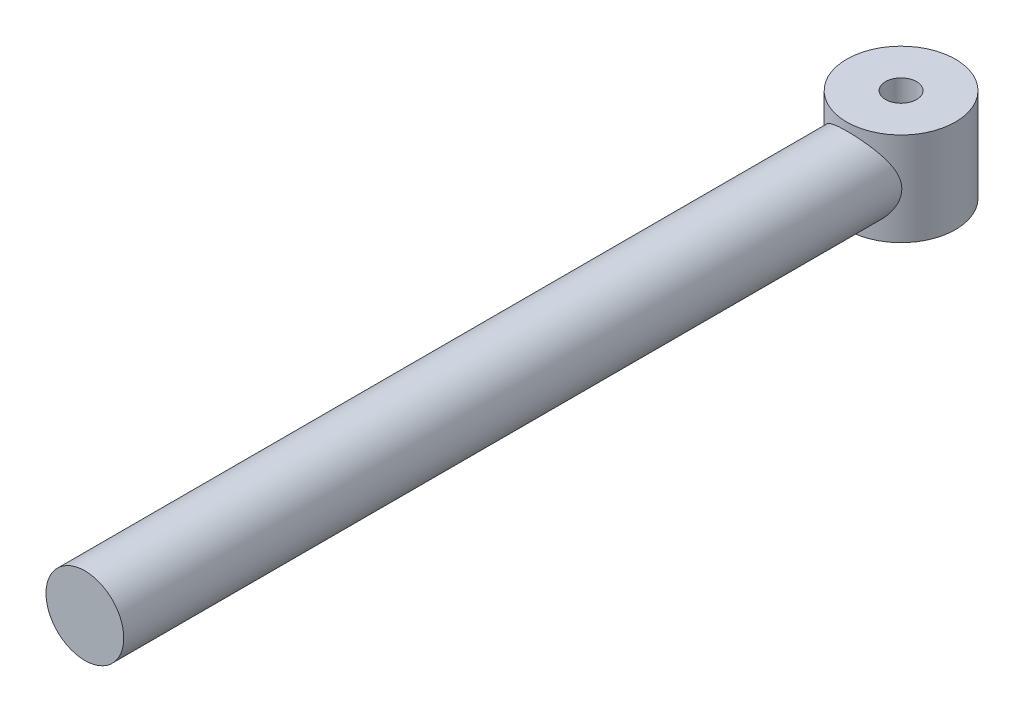
SolidWorks part; units mm, degrees
ref_plane "Front Plane" through (0, 0, 0) normal (0, 0, 1) x (1, 0, 0)
ref_plane "Top Plane" through (0, 0, 0) normal (0, 1, 0) x (1, 0, 0)
ref_plane "Right Plane" through (0, 0, 0) normal (1, 0, 0) x (0, 0, -1)
sketch "Sketch1" plane through (0, 0, 0) normal (0, 0, 1) x (1, 0, 0)
  circle A0 centre (0, 0) radius 25
  dimension "D1" = 50
extrude "Boss-Extrude1" add sketch "Sketch1" along normal blind 525
sketch "Sketch2" plane through (0, 0, 0) normal (0, 1, 0) x (1, 0, 0)
  circle A0 centre (0, 0) radius 10
  circle A1 centre (0, 0) radius 35
  dimension "D1" = 70
  dimension "D2" = 20
extrude "Boss-Extrude2" add sketch "Sketch2" along normal mid plane 60
extrude "Cut-Extrude1" cut sketch "Sketch2<2>" against normal through all both and the other way through all contours A0
sketch "Sketch2<2>" plane through (0, 0, 0) normal (0, 1, 0) x (1, 0, 0) same geometry as "Sketch2"
